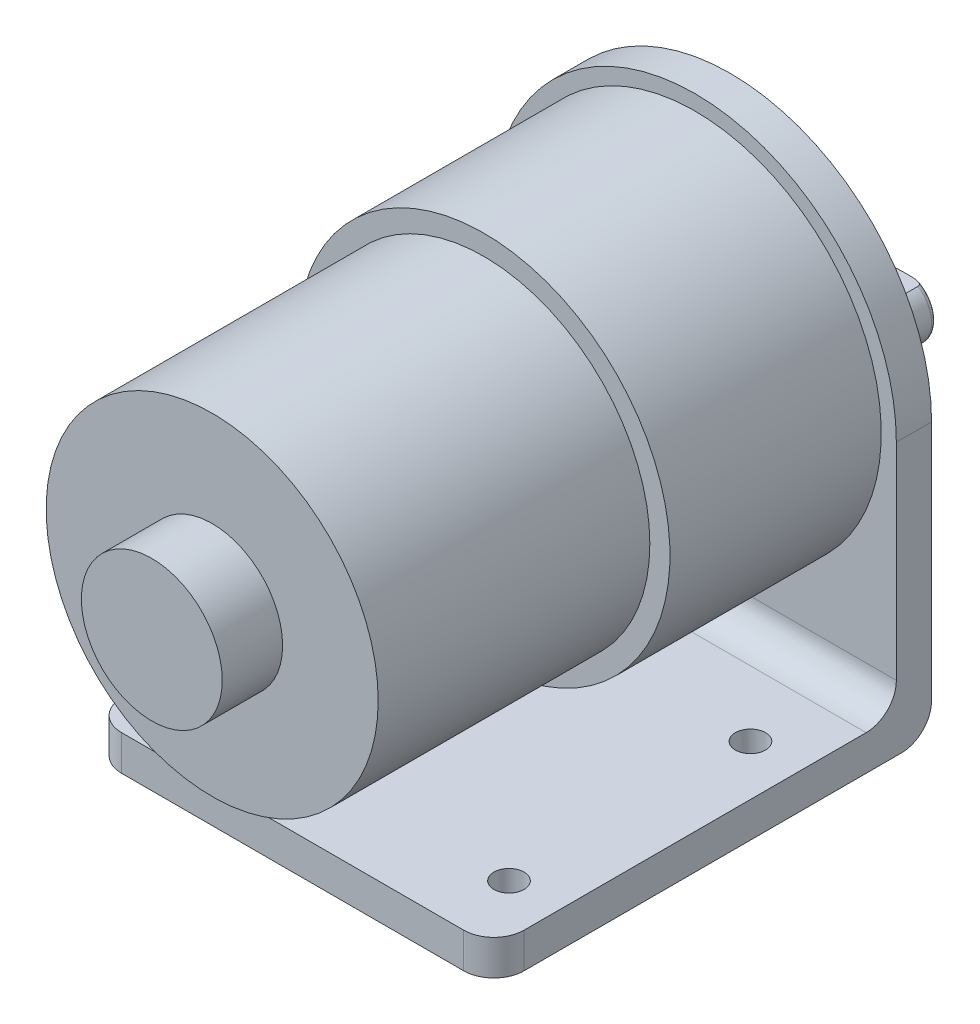
SolidWorks part; units mm, degrees
ref_plane "Front Plane" through (0, 0, 0) normal (0, 0, 1) x (1, 0, 0)
ref_plane "Top Plane" through (0, 0, 0) normal (0, 1, 0) x (1, 0, 0)
ref_plane "Right Plane" through (0, 0, 0) normal (1, 0, 0) x (0, 0, -1)
sketch "Sketch1" plane through (0, 0, 0) normal (0, 0, 1) x (1, 0, 0)
  circle A0 centre (0, 0) radius 18.5
  dimension "D1" = 37
extrude "Boss-Extrude1" add sketch "Sketch1" along normal blind 21
sketch "Sketch2" plane through (0, 0, 21) normal (0, 0, 1) x (1, 0, 0)
  circle A0 centre (0, 0) radius 16.5
  dimension "D1" = 33
extrude "Boss-Extrude2" add sketch "Sketch2" along normal blind 27
sketch "Sketch3" plane through (0, 0, 48) normal (0, 0, 1) x (1, 0, 0)
  circle A0 centre (0, 0) radius 7
  dimension "D1" = 14
extrude "Boss-Extrude3" add sketch "Sketch3" along normal blind 6
sketch "Sketch4" plane through (0, 0, 0) normal (0, 0, -1) x (-1, 0, 0)
  line L0 (-49.374, -27) -> (58.383, -27) construction
  line L1 (-20, 0) -> (-20, -27)
  line L2 (20, 0) -> (20, -27)
  line L3 (20, -27) -> (-20, -27)
  line L4 (0, 27.963) -> (0, -32.292) construction
  line L5 (0, 5) -> (0, -8.5) construction
  line L6 (6.5, 5) -> (6.5, -8.5)
  line L7 (-6.5, 5) -> (-6.5, -8.5)
  arc A0 (20, 0) -> (-20, 0) centre (0, 0) ccw
  arc A1 (-20, 0) -> (20, 0) centre (0, 0) ccw construction
  arc A2 (6.5, 5) -> (-6.5, 5) centre (0, 5) ccw
  arc A3 (-6.5, -8.5) -> (6.5, -8.5) centre (0, -8.5) ccw
  point P12 (0, -1.75)
  dimension "D1" = 40
  dimension "D3" = 13
  dimension "D2" = 27
  dimension "D4" = 32
  dimension "D5" = 18.5
extrude "Boss-Extrude4" add sketch "Sketch4" along normal blind 3.5
sketch "Sketch5" plane through (0, 0, 0) normal (0, 0, 1) x (1, 0, 0)
  line L0 (20, -27) -> (-20, -27) construction
  line L1 (20, -27) -> (-20, -27)
  line L2 (-20, -27) -> (-20, -23.5)
  line L3 (-20, -27) -> (-20, 0) construction
  line L4 (-20, -23.5) -> (20, -23.5)
  line L5 (20, 0) -> (20, -27) construction
  line L6 (20, -23.5) -> (20, -27)
  dimension "D1" = 3.5
extrude "Boss-Extrude5" add sketch "Sketch5" along normal blind 40
fillet "Fillet1" radius 3 4 edges at (0, -27, -3.5) (0, -23.5, 0) (-20, -25.25, 40) (20, -25.25, 40)
sketch "Sketch6" plane through (0, 0, 0) normal (0, 0, -1) x (-1, 0, 0)
  arc A1 (-6.5, -8.5) -> (6.5, -8.5) centre (0, -8.5) ccw construction
  circle A2 centre (0, -8.5) radius 6
  arc A3 (-6.5, -8.5) -> (6.5, -8.5) centre (0, -8.5) ccw construction
  point P5 (0, 0)
  dimension "D1" = 12
extrude "Boss-Extrude6" add sketch "Sketch6" along normal blind 6
sketch "Sketch7" plane through (0, 0, -6) normal (0, 0, -1) x (-1, 0, 0)
  circle A0 centre (0, -8.5) radius 6 construction
  circle A1 centre (0, -8.5) radius 6 construction
  circle A2 centre (0, -8.5) radius 3
  dimension "D1" = 6
extrude "Boss-Extrude7" add sketch "Sketch7" along normal blind 15
fillet "Fillet2" radius 0.5 1 edges at (-3, -8.5, -21)
sketch "Sketch8" plane through (0, 0, -21) normal (0, 0, -1) x (-1, 0, 0)
  line L0 (-1.6583, -6) -> (1.6583, -6)
  circle A0 centre (0, -8.5) radius 3 construction
  arc A1 (1.6583, -6) -> (-1.6583, -6) centre (0, -8.5) ccw
  arc A2 (-1.6583, -6) -> (1.6583, -6) centre (0, -8.5) ccw construction
  dimension "D1" = 2.5
extrude "Cut-Extrude1" cut sketch "Sketch8" against normal blind 12
sketch "Sketch9" plane through (0, -27, 0) normal (0, -1, 0) x (1, 0, 0)
  line L0 (0, 0) -> (0, 74.3316) construction
  line L1 (-17, 40) -> (17, 40) construction
  line L2 (-17, 40) -> (17, 40) construction
  line L3 (15, 40) -> (15, 4.9666) construction
  circle A0 centre (15, 33.5) radius 1.5
  circle A1 centre (15, 9.5) radius 1.5
  circle A2 centre (-15, 33.5) radius 1.5
  circle A3 centre (-15, 9.5) radius 1.5
  dimension "D2" = 3
  dimension "D1" = 15
  dimension "D3" = 6.5
  dimension "D4" = 30.5
extrude "Cut-Extrude2" cut sketch "Sketch9" against normal up to next
